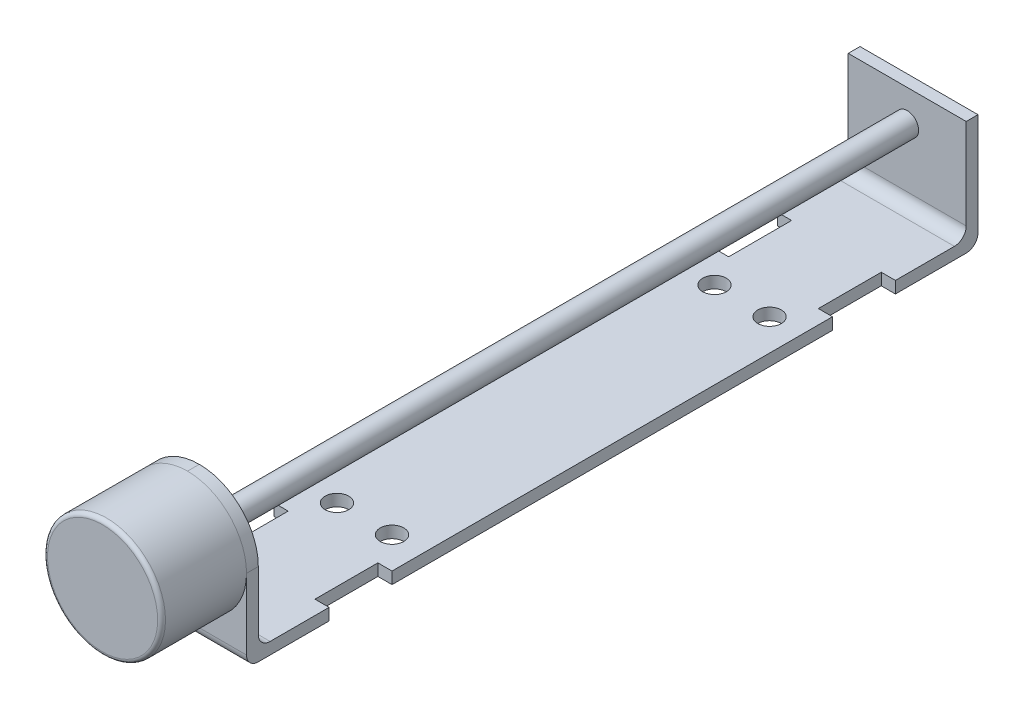
SolidWorks part; units mm, degrees
ref_plane "Plan de face" through (0, 0, 0) normal (0, 0, 1) x (1, 0, 0)
ref_plane "Plan de dessus" through (0, 0, 0) normal (0, 1, 0) x (1, 0, 0)
ref_plane "Plan de droite" through (0, 0, 0) normal (1, 0, 0) x (0, 0, -1)
sketch "Esquisse1" plane through (0, 0, 0) normal (1, 0, 0) x (0, 0, -1)
  line L0 (-46.5, 0) -> (46.5, 0)
  line L1 (46.5, 0) -> (46.5, 14.5)
  line L2 (46.5, 14.5) -> (45, 14.5)
  line L3 (45, 14.5) -> (45, 1.5)
  line L4 (45, 1.5) -> (-45, 1.5)
  line L5 (-45, 1.5) -> (-45, 18)
  line L6 (-45, 18) -> (-46.5, 18)
  line L7 (-46.5, 18) -> (-46.5, 0)
  line L8 (0, 0) -> (0, 17.2551) construction
  dimension "D1" = 18
  dimension "D2" = 14.5
  dimension "D3" = 93
  dimension "D4" = 1.5
  dimension "D5" = 1.5
  dimension "D6" = 1.5
extrude "Boss.-Extru.1" add sketch "Esquisse1" along normal blind 15
fillet "Congé1" radius 1.5 4 edges at (7.5, 1.5, -45) (7.5, 0, -46.5) (7.5, 1.5, 45) (7.5, 0, 46.5)
sketch "Esquisse2" plane through (0, 0, 46.5) normal (0, 0, 1) x (1, 0, 0)
  line L0 (7.5, 18) -> (7.5, 1.5) construction
  line L1 (15, 18) -> (0, 18) construction
  line L2 (0, 1.5) -> (15, 1.5) construction
  circle A0 centre (7.5, 10.5) radius 7.5
  dimension "D1" = 15
extrude "Boss.-Extru.2" add sketch "Esquisse2" along normal blind 10.8
fillet "Congé2" radius 7.5 2 edges at (0, 18, 45.75) (15, 18, 45.75)
sketch "Esquisse3" plane through (0, 0, 0) normal (0, -1, 0) x (1, 0, 0)
  line L0 (0, 0) -> (15, 0) construction
  line L1 (15, 45) -> (15, -45) construction
  line L2 (7.5, 0) -> (7.5, 45) construction
  line L3 (15, 45) -> (0, 45) construction
  line L4 (0, 45) -> (0, -45) construction
  line L5 (0, 36) -> (1.8, 36)
  line L6 (0, 36) -> (0, 28)
  line L7 (0, 28) -> (1.8, 28)
  line L8 (1.8, 36) -> (1.8, 28)
  line L9 (13.2, 36) -> (13.2, 28)
  line L10 (15, 28) -> (13.2, 28)
  line L11 (15, 36) -> (15, 28)
  line L12 (15, 36) -> (13.2, 36)
  line L13 (15, -36) -> (13.2, -36)
  line L14 (15, -36) -> (15, -28)
  line L15 (15, -28) -> (13.2, -28)
  line L16 (13.2, -36) -> (13.2, -28)
  line L17 (1.8, -36) -> (1.8, -28)
  line L18 (0, -28) -> (1.8, -28)
  line L19 (0, -36) -> (0, -28)
  line L20 (0, -36) -> (1.8, -36)
  circle A0 centre (4, 24) radius 1.5
  circle A1 centre (11, 24) radius 1.5
  circle A2 centre (4, -24) radius 1.5
  circle A3 centre (11, -24) radius 1.5
  dimension "D1" = 3
  dimension "D2" = 24
  dimension "D3" = 3.5
  dimension "D4" = 1.8
  dimension "D5" = 8
  dimension "D6" = 28
extrude "Enlèv. mat.-Extru.1" cut sketch "Esquisse3" against normal through all
sketch "Esquisse4" plane through (0, 0, 45) normal (0, 0, -1) x (-1, 0, 0)
  circle A0 centre (-7.5, 10.5) radius 1.45
  dimension "D1" = 2.9
extrude "Boss.-Extru.3" add sketch "Esquisse4" along normal up to surface (90 mm away) up to face at (7.5, 8.75, -45)
fillet "Congé3" radius 0.5 1 edges at (15, 10.5, 57.3)
